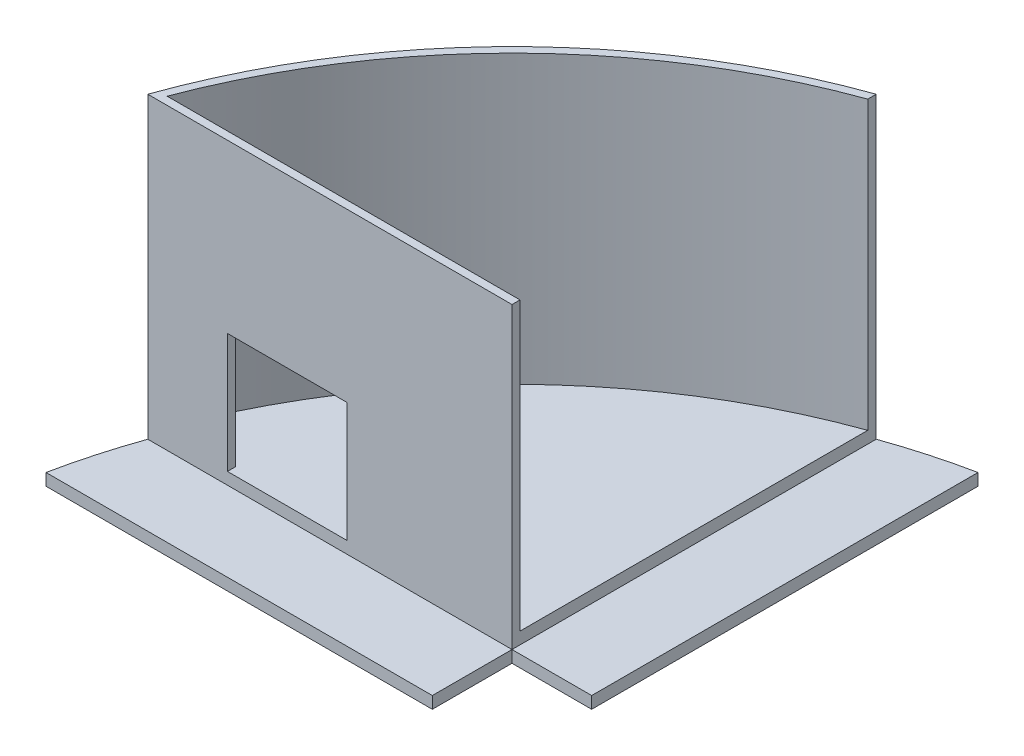
SolidWorks part; units mm, degrees
ref_plane "Front Plane" through (0, 0, 0) normal (0, 0, 1) x (1, 0, 0)
ref_plane "Top Plane" through (0, 0, 0) normal (0, 1, 0) x (1, 0, 0)
ref_plane "Right Plane" through (0, 0, 0) normal (1, 0, 0) x (0, 0, -1)
sketch "Sketch1" plane through (0, 0, 0) normal (0, 1, 0) x (1, 0, 0)
  line L6 (-30, 50) -> (-141.4214, 50)
  line L7 (-50, 30) -> (-146.9694, 30)
  line L8 (-50, 30) -> (-50, 141.4214)
  line L9 (-30, 50) -> (-30, 146.9694)
  arc A0 (-30, 146.9694) -> (-146.9694, 30) centre (0, 0) ccw
  dimension "D1" = 300
extrude "Boss-Extrude1" add sketch "Sketch1" along normal blind 3 contours L8 A0 L6 | L6 A0 L7 L8 | L9 A0 L8 L6 region at (-39.9022, 0, -97.2357) region at (-97.2357, 0, -39.9022) region at (-85.0087, 0, -85.0087)
sketch "Sketch2" plane through (0, 3, 0) normal (0, 1, 0) x (-1, 0, 0)
  line L0 (50, -50) -> (141.4214, -50)
  line L1 (50, -50) -> (50, -141.4214)
  arc A0 (30, -146.9694) -> (146.9694, -30) centre (0, 0) ccw construction
  arc A1 (141.4214, -50) -> (50, -141.4214) centre (0, 0) cw
extrude "Boss-Extrude2" add sketch "Sketch2" along normal blind 75
shell "Shell1" thickness 2 removed face at (-50, 49.875, -84.283)
sketch "Sketch3" plane through (0, 78, 0) normal (0, 1, 0) x (-1, 0, 0)
  line L0 (138.5641, -52) -> (50, -52)
  line L1 (50, -52) -> (50, -139.2982)
  arc A0 (50, -139.2982) -> (138.5641, -52) centre (0, 0) ccw
  line M1 (50, -50) -> (50, -141.4214)
extrude "Cut-Extrude1" cut sketch "Sketch3" against normal blind 2 contours A0 L0 M1 region at (-83.7804, 78, -85.323)
sketch "Sketch4" plane through (0, 0, 0) normal (0, -1, 0) x (1, 0, 0)
  line L0 (-50, -52) -> (-50, -139.2982)
  line L1 (-50, -139.2982) -> (-50, -52)
  line L2 (-50, -52) -> (-138.5641, -52)
  arc A0 (-138.5641, -52) -> (-50, -139.2982) centre (0, 0) ccw
extrude "Boss-Extrude3" add sketch "Sketch4" against normal blind 6 contours L2 A0 L0 region at (-83.7804, 0, -85.323)
sketch "Sketch5" plane through (0, 0, -50) normal (0, 0, 1) x (1, 0, 0)
  line L0 (-121.4214, 36) -> (-121.4214, 6)
  line L1 (-121.4214, 6) -> (-91.4214, 6)
  line L2 (-91.4214, 6) -> (-91.4214, 36)
  line L3 (-91.4214, 36) -> (-121.4214, 36)
  line L4 (-141.4214, 3) -> (-50, 3) construction
  line L5 (-141.4214, 78) -> (-141.4214, 3) construction
  dimension "D1" = 3
  dimension "D2" = 20
  dimension "D3" = 30
  dimension "D4" = 30
extrude "Cut-Extrude2" cut sketch "Sketch5" against normal blind 2 contours L2 L3 L0 L1 region at (-106.4214, 21, -50)
